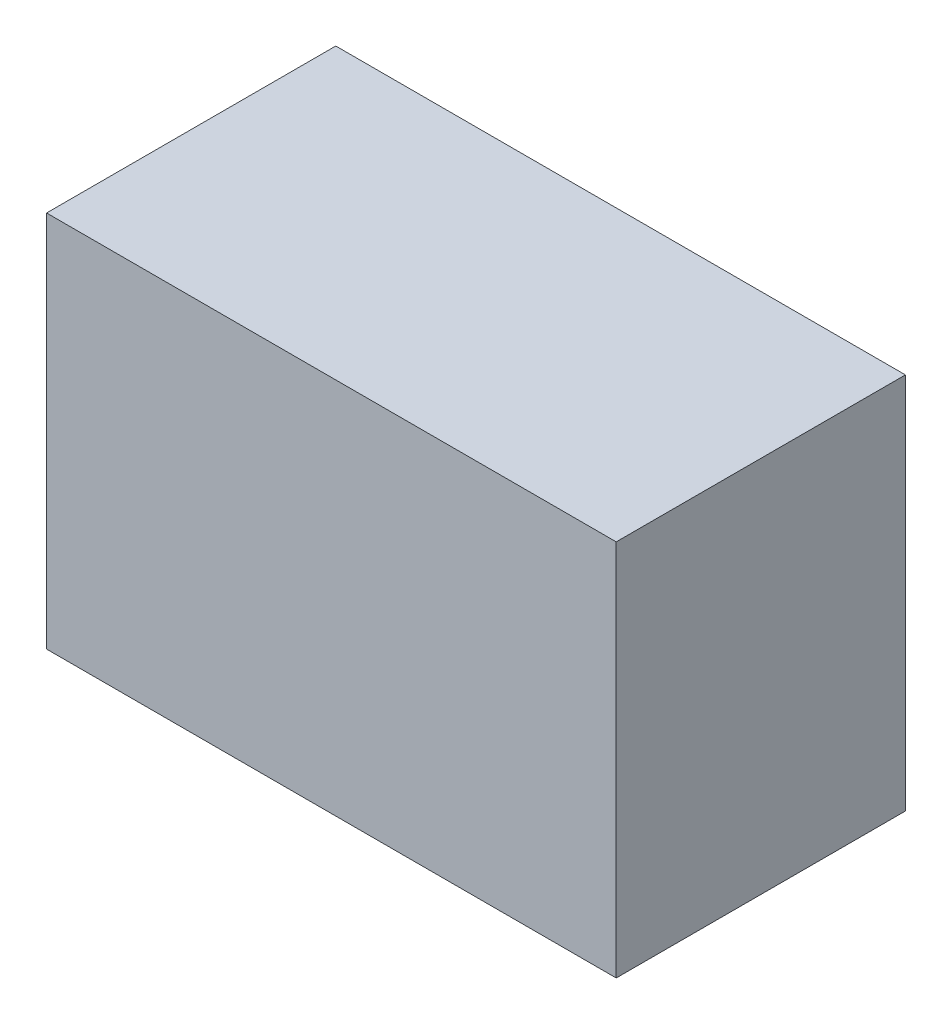
SolidWorks part; units mm, degrees
material "ABS"
ref_plane "Front Plane" through (0, 0, 0) normal (0, 0, 1) x (1, 0, 0)
ref_plane "Top Plane" through (0, 0, 0) normal (0, 1, 0) x (1, 0, 0)
ref_plane "Right Plane" through (0, 0, 0) normal (1, 0, 0) x (0, 0, -1)
sketch "Sketch1" plane through (0, 0, 0) normal (0, 1, 0) x (1, 0, 0)
  line L1 (-82.55, -41.91) -> (82.55, -41.91)
  line L2 (-82.55, -41.91) -> (-82.55, 41.91)
  line L3 (-82.55, 41.91) -> (82.55, 41.91)
  line L4 (82.55, -41.91) -> (82.55, 41.91)
  line L5 (-82.55, -41.91) -> (82.55, 41.91) construction
  line L6 (-82.55, 41.91) -> (82.55, -41.91) construction
  point P0 (0, 0)
  dimension "D1" = 83.82
  dimension "D2" = 165.1
extrude "Boss-Extrude1" add sketch "Sketch1" along normal blind 109.474
sketch "Sketch2" plane through (0, 109.474, 0) normal (0, 1, 0) x (1, 0, 0)
  line L0 (-82.55, -41.91) -> (82.55, 41.91) construction
  line L1 (-82.55, 41.91) -> (-82.55, -41.91) construction
  line L2 (-82.55, -41.91) -> (82.55, -41.91) construction
  line L3 (82.55, 41.91) -> (-82.55, 41.91) construction
  line L4 (82.55, -41.91) -> (82.55, 41.91) construction
  circle A0 centre (0, 0) radius 13.5342 construction
  dimension "D1" = 27.0684
